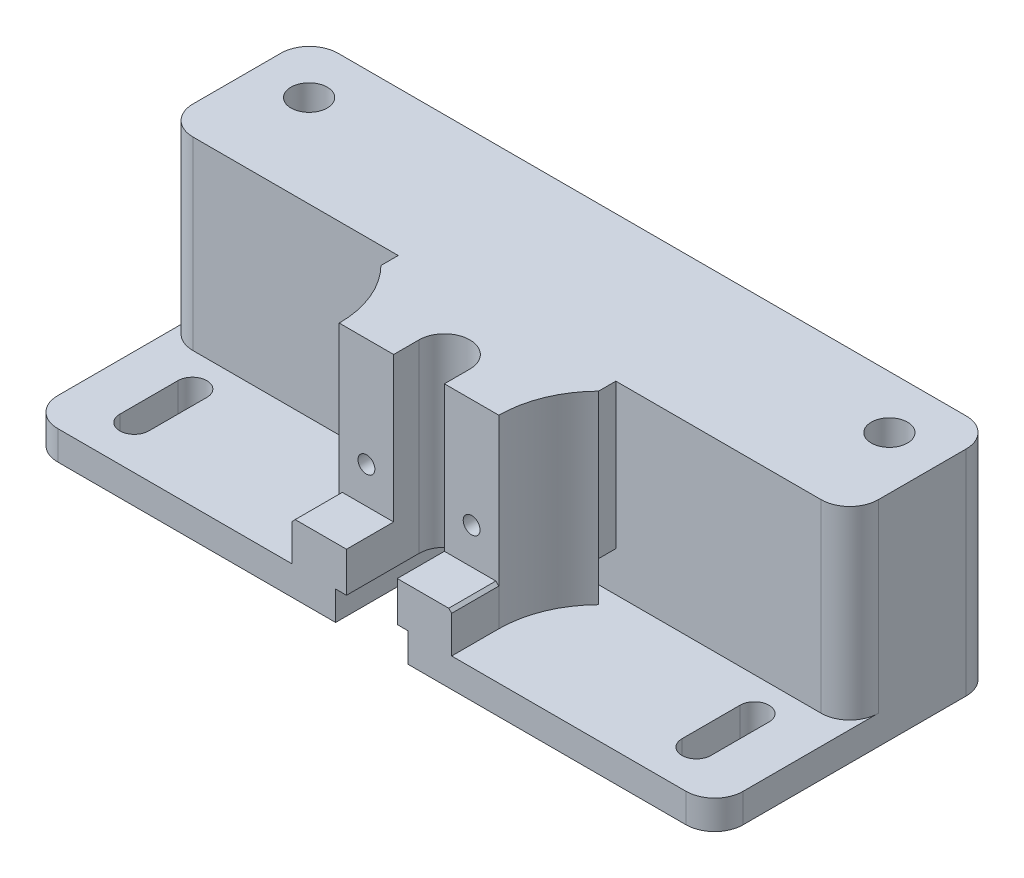
SolidWorks part; units mm, degrees
ref_plane "Front Plane" through (0, 0, 0) normal (0, 0, 1) x (1, 0, 0)
ref_plane "Top Plane" through (0, 0, 0) normal (0, 1, 0) x (1, 0, 0)
ref_plane "Right Plane" through (0, 0, 0) normal (1, 0, 0) x (0, 0, -1)
ref_plane "Plane1" through (0, 0, -20.6375) normal (0, 0, -1) x (-1, 0, 0)
sketch "Sketch1" plane through (0, 0, -20.6375) normal (0, 0, -1) x (-1, 0, 0)
  line L0 (19.05, 0) -> (19.05, 25.4)
  line L1 (19.05, 25.4) -> (-19.05, 25.4)
  line L2 (-19.05, 25.4) -> (-19.05, 0)
  line L3 (-19.05, 0) -> (19.05, 0)
extrude "Boss-Extrude1" add sketch "Sketch1" against normal blind 25.0825
ref_plane "Plane2" through (0, 0, -2.2225) normal (0, 0, 1) x (1, 0, 0)
sketch "Sketch6" plane through (0, 0, -2.2225) normal (0, 0, 1) x (1, 0, 0)
  line L0 (-6.0325, 8.1831) -> (-9.2075, 10.0162)
  line L1 (-9.2075, 10.0162) -> (-12.3825, 8.1831)
  line L2 (-12.3825, 8.1831) -> (-12.3825, 4.5169)
  line L3 (-12.3825, 4.5169) -> (-9.2075, 2.6838)
  line L4 (-9.2075, 2.6838) -> (-6.0325, 4.5169)
  line L5 (-6.0325, 4.5169) -> (-6.0325, 8.1831)
extrude "Cut-Extrude1" cut sketch "Sketch6" against normal blind 2.3876
sketch "Sketch12" plane through (0, 0, -2.2225) normal (0, 0, 1) x (1, 0, 0)
  line L0 (6.0325, 8.1831) -> (6.0325, 4.5169)
  line L1 (6.0325, 4.5169) -> (9.2075, 2.6838)
  line L2 (9.2075, 2.6838) -> (12.3825, 4.5169)
  line L3 (12.3825, 4.5169) -> (12.3825, 8.1831)
  line L4 (12.3825, 8.1831) -> (9.2075, 10.0162)
  line L5 (9.2075, 10.0162) -> (6.0325, 8.1831)
extrude "Cut-Extrude2" cut sketch "Sketch12" against normal blind 2.3876
ref_plane "Plane3" through (0, 0, 0) normal (0, -1, 0) x (-1, 0, 0)
sketch "Sketch18" plane through (0, 0, 0) normal (0, -1, 0) x (-1, 0, 0)
  line L0 (13.97, -4.445) -> (19.05, -4.445)
  line L1 (19.05, -4.445) -> (19.05, 7.9375)
  arc A0 (19.05, 7.9375) -> (13.97, -4.445) centre (31.6012, -4.445) ccw
extrude "Cut-Extrude3" cut sketch "Sketch18" against normal through all
sketch "Sketch19" plane through (0, 0, 0) normal (0, -1, 0) x (1, 0, 0)
  line L0 (4.445, 4.445) -> (-4.445, 4.445)
  line L1 (-4.445, 4.445) -> (-4.445, 0)
  line L2 (4.445, 0) -> (4.445, 4.445)
  arc A0 (-4.445, 0) -> (4.445, 0) centre (0, 0) ccw
extrude "Cut-Extrude4" cut sketch "Sketch19" against normal through all
sketch "Sketch20" plane through (0, 0, 0) normal (0, -1, 0) x (1, 0, 0)
  line L0 (19.05, -7.9375) -> (19.05, 4.445)
  line L1 (19.05, 4.445) -> (13.97, 4.445)
  arc A0 (13.97, 4.445) -> (19.05, -7.9375) centre (31.6012, 4.445) ccw
extrude "Cut-Extrude5" cut sketch "Sketch20" against normal through all
sketch "Sketch21" plane through (0, 0, 0) normal (0, -1, 0) x (1, 0, 0)
  line L0 (4.445, 0) -> (4.445, 12.7)
  line L1 (4.445, 12.7) -> (13.97, 12.7)
  line L2 (13.97, 12.7) -> (13.97, 4.445)
  line L3 (19.05, -7.9375) -> (-19.05, -7.9375)
  line L4 (-13.97, 4.445) -> (-13.97, 12.7)
  line L5 (-13.97, 12.7) -> (-4.445, 12.7)
  line L6 (-4.445, 12.7) -> (-4.445, 0)
  arc A0 (13.97, 4.445) -> (19.05, -7.9375) centre (31.6012, 4.445) ccw
  arc A1 (-19.05, -7.9375) -> (-13.97, 4.445) centre (-31.6012, 4.445) ccw
  arc A2 (-4.445, 0) -> (4.445, 0) centre (0, 0) ccw
extrude "Boss-Extrude2" add sketch "Sketch21" along normal blind 6.985
sketch "Sketch22" plane through (0, -6.985, 0) normal (0, -1, 0) x (1, 0, 0)
  line L0 (-4.445, -6.35) -> (4.445, -6.35)
  line L1 (4.445, -6.35) -> (4.445, 12.7)
  line L2 (4.445, 12.7) -> (60, 12.7)
  line L3 (60, 12.7) -> (60, -12.7)
  line L4 (60, -12.7) -> (-60, -12.7)
  line L5 (-60, -12.7) -> (-60, 12.7)
  line L6 (-60, 12.7) -> (-4.445, 12.7)
  line L7 (-4.445, 12.7) -> (-4.445, -6.35)
  point P8 (0, -12.7)
  dimension "D1" = 25.4
  dimension "D2" = 120
  dimension "D3" = 8.89
  dimension "D4" = 4.445
extrude "Boss-Extrude3" add sketch "Sketch22" along normal blind 5.08
ref_plane "Plane4" through (4.445, 0, 0) normal (-1, 0, 0) x (0, 0, 1)
sketch "Sketch29" plane through (4.445, 0, 0) normal (-1, 0, 0) x (0, 0, 1)
  line L0 (12.7, -6.985) -> (-6.35, -6.985)
  line L1 (-6.35, -6.985) -> (-6.35, -12.065)
  line L2 (-6.35, -12.065) -> (12.7, -12.065)
  line L3 (12.7, -12.065) -> (12.7, -6.985)
extrude "Cut-Extrude6" cut sketch "Sketch29" against normal blind 1.905
sketch "Sketch30" plane through (-4.445, 0, 0) normal (1, 0, 0) x (0, 0, -1)
  line L0 (-12.7, -6.985) -> (-12.7, -12.065)
  line L1 (-12.7, -12.065) -> (6.35, -12.065)
  line L2 (6.35, -12.065) -> (6.35, -6.985)
  line L3 (6.35, -6.985) -> (-12.7, -6.985)
extrude "Cut-Extrude7" cut sketch "Sketch30" against normal blind 1.905
ref_plane "Plane5" through (0, -12.065, 0) normal (0, -1, 0) x (-1, 0, 0)
sketch "Sketch48" plane through (0, -12.065, 0) normal (0, -1, 0) x (-1, 0, 0)
  line L0 (-51.7525, 5.08) -> (-51.7525, -5.08)
  line L1 (-46.6725, -5.08) -> (-46.6725, 5.08)
  arc A0 (-46.6725, 5.08) -> (-51.7525, 5.08) centre (-49.2125, 5.08) ccw
  arc A1 (-51.7525, -5.08) -> (-46.6725, -5.08) centre (-49.2125, -5.08) ccw
extrude "Cut-Extrude10" cut sketch "Sketch48" against normal up to next
sketch "Sketch57" plane through (0, -12.065, 0) normal (0, -1, 0) x (-1, 0, 0)
  line L0 (46.6725, 5.08) -> (46.6725, -5.08)
  line L1 (51.7525, -5.08) -> (51.7525, 5.08)
  arc A0 (51.7525, 5.08) -> (46.6725, 5.08) centre (49.2125, 5.08) ccw
  arc A1 (46.6725, -5.08) -> (51.7525, -5.08) centre (49.2125, -5.08) ccw
extrude "Cut-Extrude11" cut sketch "Sketch57" against normal up to next
ref_plane "Plane6" through (0, 6.35, 0) normal (0, 1, 0) x (1, 0, 0)
sketch "Sketch67" plane through (0, 6.35, 0) normal (0, 1, 0) x (1, 0, 0)
  line L0 (-7.7343, 20.6375) -> (-9.2075, 20.6375)
  line L1 (-9.2075, 20.6375) -> (-9.2075, 4.6101)
  line L2 (-9.2075, 4.6101) -> (-7.7343, 4.6101)
  line L3 (-7.7343, 4.6101) -> (-7.7343, 20.6375)
  line L4 (-9.2075, 20.6375) -> (-9.2075, 4.6101) construction
revolve "Cut-Revolve1" cut sketch "Sketch67" angle 360 about L1 reverse direction yes
sketch "Sketch77" plane through (0, 6.35, 0) normal (0, 1, 0) x (1, 0, 0)
  line L0 (10.6807, 20.6375) -> (9.2075, 20.6375)
  line L1 (9.2075, 20.6375) -> (9.2075, 4.6101)
  line L2 (9.2075, 4.6101) -> (10.6807, 4.6101)
  line L3 (10.6807, 4.6101) -> (10.6807, 20.6375)
  line L4 (9.2075, 20.6375) -> (9.2075, 4.6101) construction
revolve "Cut-Revolve2" cut sketch "Sketch77" angle 360 about L1 reverse direction yes
hole_wizard "M2.5 Clearance Hole1" positions "Sketch79" profile "Sketch78" hole size "M2.5" standard "ANSI Metric"
sketch "Sketch79" plane through (0, 0, 4.445) normal (0, 0, 1) x (1, 0, 0)
  point P0 (9.2075, 6.35)
  point P1 (-9.2075, 6.35)
sketch "Sketch78" plane through (9.2075, 6.35, 4.445) normal (1, 0, 0) x (0, -1, 0)
  line L0 (0, 0) -> (0, 25.0825)
  line L1 (0, 25.0825) -> (1.4732, 25.0825)
  line L2 (1.4732, 25.0825) -> (1.4732, 0)
  line L5 (1.4732, 0) -> (0, 0)
  line L11 (0, -6.35) -> (0, 107.95) construction
  dimension "Thru Hole Dia." = 2.9464
  dimension "Thru Hole Depth" = 25.0825
chamfer "Chamfer1" distance 0.5111 angle 45.61 1 edges at (13.97, 0, 8.5725) first distance on face at (13.97, -3.4925, 8.5725)
chamfer "Chamfer2" distance 0.5582 angle 43.977 1 edges at (-13.97, 0, 8.5725) first distance on face at (-13.97, -3.4925, 8.5725)
sketch "Sketch80" plane through (0, 0, -20.6375) normal (0, 0, -1) x (-1, 0, 0)
  line L0 (-19.05, 25.4) -> (19.05, 25.4)
  line L1 (-19.05, 25.4) -> (-19.05, 0)
  line L2 (-19.05, 0) -> (19.05, 0)
  line L3 (19.05, 25.4) -> (19.05, 0)
extrude "Cut-Extrude13" cut sketch "Sketch80" against normal up to surface (7.9375 mm away) up to face at (0, -9.525, -12.7)
sketch "Sketch81" plane through (0, 25.4, 0) normal (0, 1, 0) x (1, 0, 0)
  line L0 (-19.05, 12.7) -> (19.05, 12.7) construction
  line L1 (60, 10.9643) -> (-60, 10.9643)
  line L2 (60, 10.9643) -> (60, 36.3643)
  line L3 (60, 36.3643) -> (-60, 36.3643)
  line L4 (-60, 10.9643) -> (-60, 36.3643)
  point P0 (0, 12.7)
  point P7 (0, 10.9643)
  dimension "D1" = 120
  dimension "D2" = 25.4
extrude "Boss-Extrude4" add sketch "Sketch81" against normal up to surface (37.465 mm away) up to face at (-49.2125, -12.065, 0)
sketch "Sketch82" plane through (0, -12.065, 0) normal (0, -1, 0) x (1, 0, 0)
  line L0 (-42.1371, -27.1097) -> (42.1371, -27.1097) construction
  circle A0 centre (-50.8, -27.1097) radius 3.175
  circle A1 centre (50.8, -27.1097) radius 3.175
  point P3 (0, -27.1097)
  dimension "D1" = 50.8
  dimension "D3" = 6.35
  dimension "D4" = 6.35
  dimension "D2" = 50.8
extrude "Cut-Extrude14" cut sketch "Sketch82" against normal through all
fillet "Fillet3" radius 5 2 edges at (60, 6.6675, -36.3643) (-60, 6.6675, -36.3643)
fillet "Fillet4" radius 5 2 edges at (-60, 9.2075, -10.9643) (60, 9.2075, -10.9643)
fillet "Fillet5" radius 5 2 edges at (60, -9.525, 12.7) (-60, -9.525, 12.7)
